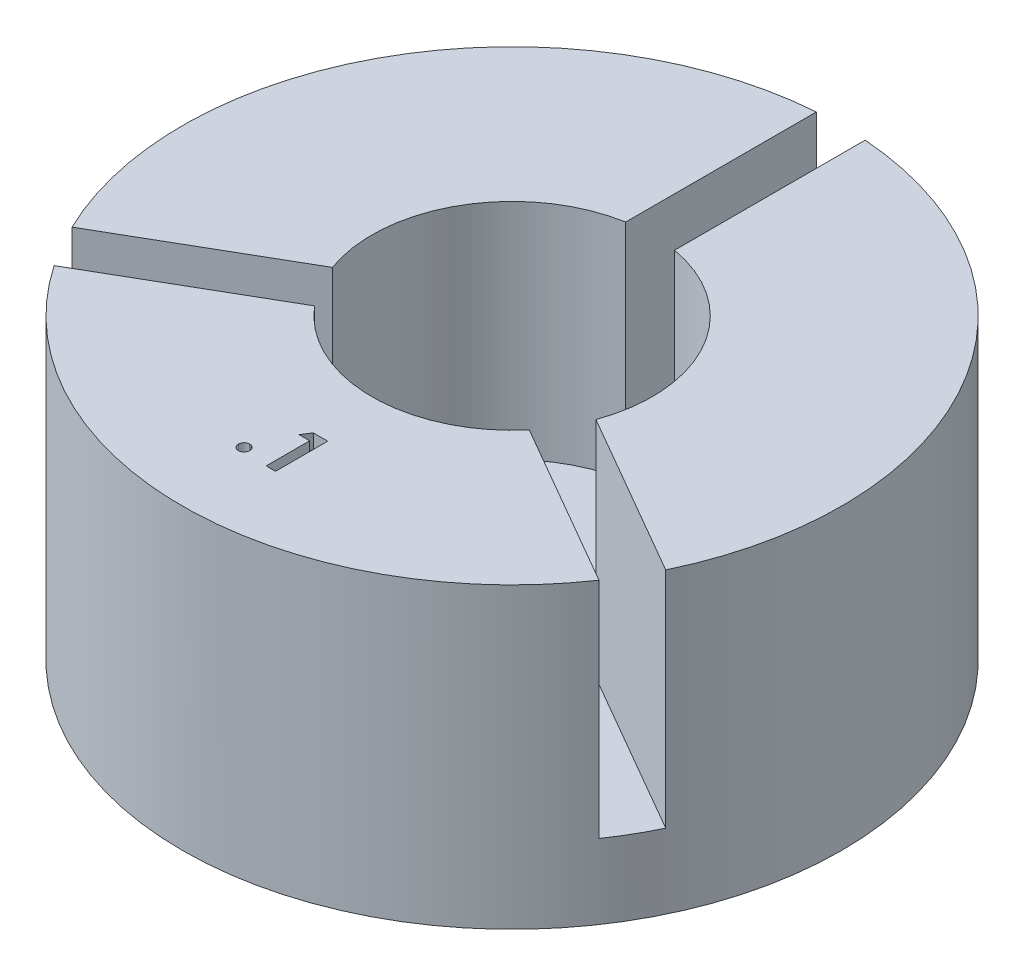
SolidWorks part; units mm, degrees
other "Markup1"
sketch "Sketch5" plane through (34.95, 15, 34.95) normal (0.0371, 0.9957, 0.0854) x (0.9174, 0, -0.3981)
ref_plane "Front Plane" through (0, 0, 0) normal (0, 0, 1) x (1, 0, 0)
ref_plane "Top Plane" through (0, 0, 0) normal (0, 1, 0) x (1, 0, 0)
ref_plane "Right Plane" through (0, 0, 0) normal (1, 0, 0) x (0, 0, -1)
sketch "Sketch2" plane through (0, 0, 0) normal (0, 1, 0) x (1, 0, 0)
  circle A0 centre (0, 0) radius 9.4
  circle A1 centre (0, 0) radius 22.1
  dimension "D1" = 18.8
  dimension "D2" = 12.7
extrude "Boss-Extrude2" add sketch "Sketch2" along normal blind 15 contours A1 A0 region at (-21.4749, 0, 0)
sketch "Sketch3" plane through (0, 0, 0) normal (0, -1, 0) x (1, 0, 0)
  circle A0 centre (0, 0) radius 22.1 construction
  circle A1 centre (0, 0) radius 22.1
extrude "Boss-Extrude3" add sketch "Sketch3" along normal blind 5
sketch "Sketch4" plane through (0, 15, 0) normal (0, 1, 0) x (1, 0, 0)
  line L0 (-1.6375, 22.0393) -> (-1.6375, 9.2563)
  line L1 (1.6375, 9.2563) -> (1.6375, 22.0393)
  line L2 (0, 0) -> (0, 24.9078) construction
  line L3 (-1.6375, 36.1723) -> (1.6375, 36.1723) construction
  circle A0 centre (0, 0) radius 22.1 construction
  circle A1 centre (0, 0) radius 9.4 construction
  arc A2 (1.6375, 22.0393) -> (-1.6375, 22.0393) centre (0, 0) ccw
  arc A3 (1.6375, 9.2563) -> (-1.6375, 9.2563) centre (0, 0) ccw
  arc A4 (-1.6375, 22.0393) -> (1.6375, 22.0393) centre (0, 0) ccw construction
  arc A5 (-1.6375, 9.2563) -> (1.6375, 9.2563) centre (0, 0) ccw construction
  point P11 (0, 36.1723)
  dimension "D1" = 3.275
extrude "Cut-Extrude1" cut sketch "Sketch4" against normal up to surface (15 mm away) up to face at (0, 0, 9.4)
pattern_circular "CirPattern1" count 3 over 360 about axis through (0, 15, 0) along (0, -1, 0) of "Cut-Extrude1" reverse direction yes
sketch "Sketch6" plane through (0, 15, 0) normal (0, 1, 0) x (1, 0, 0)
  line L0 (-7.7171, -16.9587) -> (7.7171, -16.9587) construction
  text T0 "<b>.1</b>"
  point P3 (0, -16.9587)
extrude "Cut-Extrude2" cut sketch "Sketch6" against normal blind 1
equation "\"B_OD\" = 18.7mm"
equation "\"B_ID\" = 18mm"
equation "\"B_LG\" = 9in"
equation "\"F_TH\" = 0.125in"
equation "\"C_TH\" = 0.125in"
equation "\"fins\" = 3"
equation "\"D1@Sketch2\"=\"B_OD\" + \"tol\""
equation "\"tol\" = 0.1mm"
equation "\"D1@Sketch4\"=\"F_TH\"+\"tol\""
equation "\"D1@CirPattern1\"=\"fins\""
equation "\"D1@Cut-Extrude2\"=\"tol\"*10"
